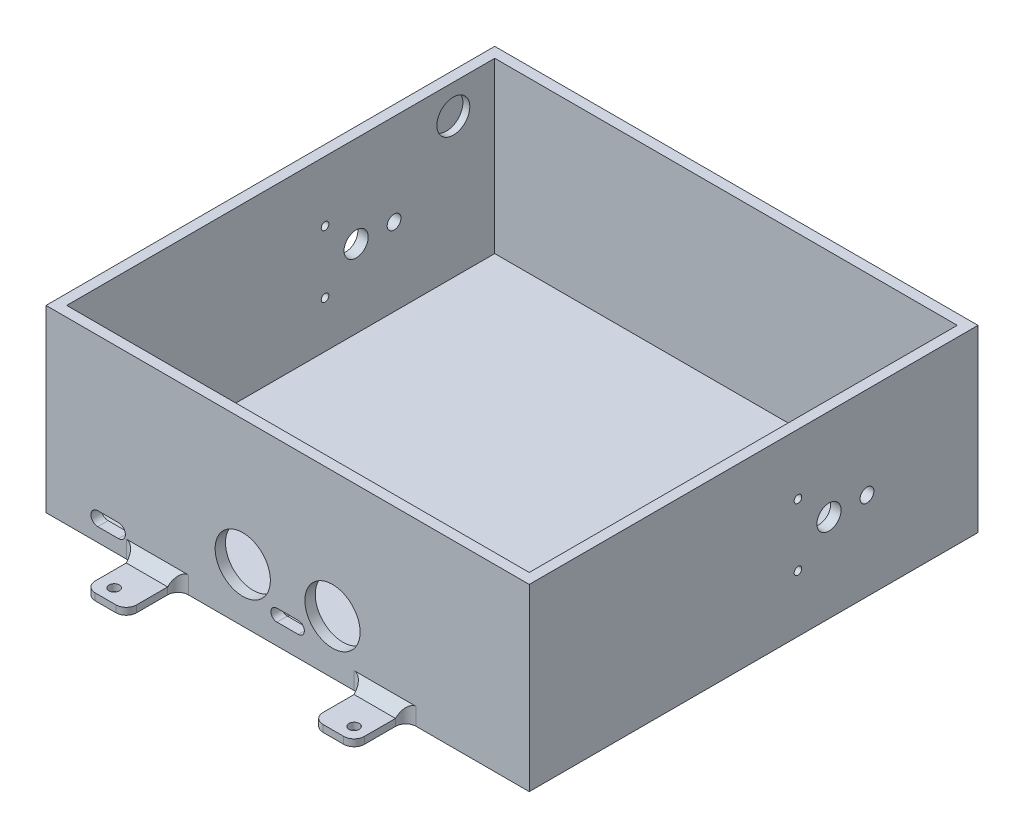
SolidWorks part; units mm, degrees
ref_plane "Front Plane" through (0, 0, 0) normal (0, 0, 1) x (1, 0, 0)
ref_plane "Top Plane" through (0, 0, 0) normal (0, 1, 0) x (1, 0, 0)
ref_plane "Right Plane" through (0, 0, 0) normal (1, 0, 0) x (0, 0, -1)
sketch "Sketch1" plane through (0, 0, 0) normal (0, 1, 0) x (1, 0, 0)
  line L1 (-70, 65) -> (70, 65)
  line L2 (-70, 65) -> (-70, -65)
  line L3 (-70, -65) -> (70, -65)
  line L4 (70, 65) -> (70, -65)
  line L5 (-70, 65) -> (70, -65) construction
  line L6 (-70, -65) -> (70, 65) construction
  point P0 (0, 0)
  dimension "D1" = 130
  dimension "D2" = 140
extrude "Boss-Extrude1" add sketch "Sketch1" along normal blind 52
shell "Shell1" thickness 3 removed face at (0, 52, 0)
sketch "Sketch2" plane through (70, 0, 0) normal (1, 0, 0) x (0, 0, -1)
  line L0 (-65, 0) -> (65, 0) construction
  line L1 (65, 52) -> (65, 0) construction
  circle A0 centre (21.8376, 25.5) radius 3.5
  circle A1 centre (32.8376, 25.5) radius 2
  circle A2 centre (12.8376, 34.5) radius 1.1
  circle A3 centre (12.8376, 16.5) radius 1.1
  dimension "D1" = 7
  dimension "D2" = 4
  dimension "D9" = 2.2
  dimension "D3" = 25.5
  dimension "D4" = 43.1624
  dimension "D5" = 11
  dimension "D6" = 18
  dimension "D7" = 9
  dimension "D8" = 52.1624
extrude "Cut-Extrude1" cut sketch "Sketch2" against normal up to surface (3 mm away) up to face at (67, 27.5, 0)
mirror "Mirror1" about plane through (0, 0, 0) normal (1, 0, 0) of "Cut-Extrude1"
sketch "Sketch3" plane through (0, 3, 0) normal (0, 1, 0) x (1, 0, 0)
  line L0 (-70, -65) -> (70, -65) construction
  line L1 (0, 0) -> (0, -122.9827) construction
  circle A0 centre (-7, -59) radius 1.1
  circle A1 centre (7, -59) radius 1.1
  dimension "D2" = 2.2
  dimension "D1" = 14
  dimension "D3" = 6
extrude "Cut-Extrude2" cut sketch "Sketch3" against normal up to surface (3 mm away) up to face at (0, 0, 0)
sketch "Sketch6" plane through (0, 0, 62) normal (0, 0, -1) x (-1, 0, 0)
  line L4 (55, 6) -> (49, 6) construction
  line L5 (55, 4) -> (49, 4)
  line L6 (55, 8) -> (49, 8)
  line L7 (70, 0) -> (-70, 0) construction
  line L8 (70, 52) -> (70, 0) construction
  arc A0 (55, 4) -> (55, 8) centre (55, 6) ccw
  arc A1 (49, 8) -> (49, 4) centre (49, 6) ccw
  point P2 (52, 6)
  dimension "D2" = 2
  dimension "D1" = 6
  dimension "D3" = 18
  dimension "D4" = 6
extrude "Cut-Extrude4" cut sketch "Sketch6" against normal up to surface (3 mm away) up to face at (0, 26, 65)
sketch "Sketch7" plane through (-67, 0, 0) normal (1, 0, 0) x (0, 0, -1)
  line L0 (62, 52) -> (62, 3) construction
  line L1 (62, 52) -> (-62, 52) construction
  circle A0 centre (50, 43.5) radius 4.775
  dimension "D1" = 9.55
  dimension "D2" = 12
  dimension "D3" = 8.5
extrude "Cut-Extrude5" cut sketch "Sketch7" against normal blind 2
ref_axis "Axis1" through (0, 54.6, 0) along (0, -1, 0)
pattern_circular "CirPattern5" count 2 every 180 about axis through (0, 54.6, 0) along (0, -1, 0) of "Cut-Extrude5"
sketch "Sketch8" plane through (0, 0, 0) normal (0, 1, 0) x (1, 0, 0)
  line L0 (-70, -65) -> (70, -65) construction
  line L1 (-43.75, -65) -> (-31.75, -65)
  line L2 (-43.75, -65) -> (-43.75, -80)
  line L3 (-43.75, -80) -> (-31.75, -80)
  line L4 (34.25, -65) -> (34.25, -80)
  line L5 (-31.75, -80) -> (-31.75, -65)
  line L6 (22.25, -80) -> (22.25, -65)
  line L7 (22.25, -80) -> (34.25, -80)
  line L8 (22.25, -65) -> (34.25, -65)
  line L9 (70, -65) -> (70, 65) construction
  dimension "D1" = 15
  dimension "D2" = 78
  dimension "D3" = 12
  dimension "D4" = 12
  dimension "D5" = 35.75
extrude "Boss-Extrude2" add sketch "Sketch8" along normal blind 2
sketch "Sketch11" plane through (0, 2, 0) normal (0, 1, 0) x (1, 0, 0)
  line L0 (-43.75, -80) -> (-31.75, -80) construction
  line L1 (-43.75, -65) -> (-43.75, -80) construction
  circle A0 centre (-39.25, -76) radius 1.5
  circle A1 centre (30.25, -76) radius 1.5
  dimension "D4" = 3
  dimension "D1" = 69.5
  dimension "D2" = 4
  dimension "D3" = 4.5
extrude "Cut-Extrude7" cut sketch "Sketch11" against normal through all
fillet "Fillet1" radius 3 4 edges at (34.25, 1, 65) (-43.75, 1, 80) (-43.75, 1, 65) (34.25, 1, 80)
fillet "Fillet2" radius 3 4 edges at (22.25, 1, 65) (22.25, 1, 80) (-31.75, 1, 65) (-31.75, 1, 80)
chamfer "Chamfer1" distance 3 angle 45 2 edges at (28.25, 2, 65) (-37.75, 2, 65)
sketch "Sketch12" plane through (0, 0, 65) normal (0, 0, 1) x (1, 0, 0)
  line L0 (-28.75, 0) -> (19.25, 0) construction
  line L1 (0, 0) -> (0, 42.7147) construction
  line L2 (-3.1, 7.75) -> (3.1, 7.75) construction
  line L3 (-3.1, 9.5) -> (3.1, 9.5)
  line L4 (-3.1, 6) -> (3.1, 6)
  circle A0 centre (-13, 15.5) radius 8
  circle A1 centre (13, 15.5) radius 8
  arc A2 (-3.1, 9.5) -> (-3.1, 6) centre (-3.1, 7.75) ccw
  arc A3 (3.1, 6) -> (3.1, 9.5) centre (3.1, 7.75) ccw
  point P11 (0, 7.75)
  point P16 (0, 0)
  dimension "D1" = 16
  dimension "D2" = 26
  dimension "D3" = 15.5
  dimension "D4" = 3.5
  dimension "D5" = 6.2
  dimension "D6" = 7.75
extrude "Cut-Extrude8" cut sketch "Sketch12" against normal blind 10
